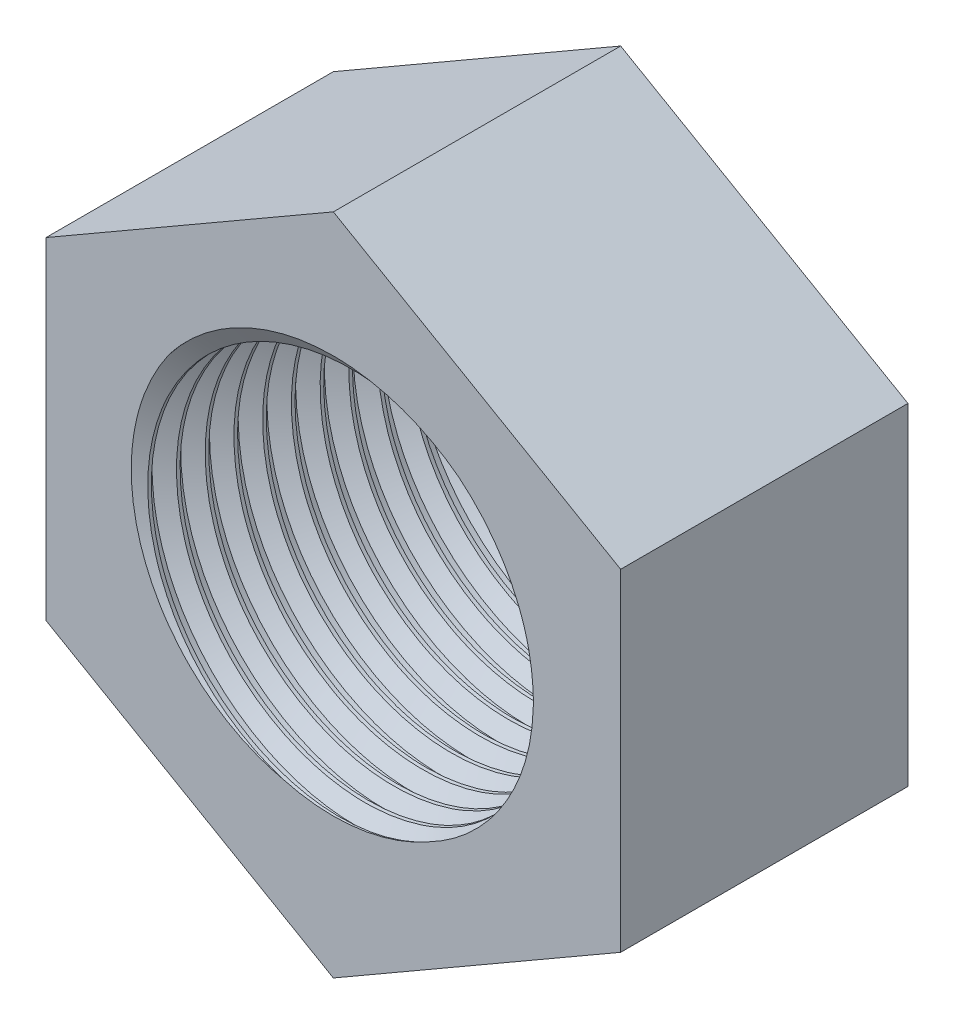
SolidWorks part; units mm, degrees
material "Ductile Iron"
ref_plane "Front Plane" through (0, 0, 0) normal (0, 0, 1) x (1, 0, 0)
ref_plane "Top Plane" through (0, 0, 0) normal (0, 1, 0) x (1, 0, 0)
ref_plane "Right Plane" through (0, 0, 0) normal (1, 0, 0) x (0, 0, -1)
sketch "Sketch1" plane through (0, 0, 0) normal (0, 0, 1) x (1, 0, 0)
  line L1 (0, -17.3205) -> (15, -8.6603)
  line L2 (15, -8.6603) -> (15, 8.6603)
  line L3 (15, 8.6603) -> (0, 17.3205)
  line L4 (0, 17.3205) -> (-15, 8.6603)
  line L5 (-15, 8.6603) -> (-15, -8.6603)
  line L6 (-15, -8.6603) -> (0, -17.3205)
  circle A0 centre (0, 0) radius 15 construction
  circle A1 centre (0, 0) radius 10
  dimension "D2" = 20
  dimension "D1" = 30
extrude "Boss-Extrude1" add sketch "Sketch1" along normal blind 15
thread "Thread1" pitch 1.5 method cut profile "Thread Profile1" start angle 0, offset 10, length 30, pitch 1.5, diameter 20
ref_plane "Plane1" through (-10, 0, 25) normal (0, 1, 0) x (1, 0, 0)
sketch "Thread Profile1" plane through (-10, 0, 25) normal (0, 1, 0) x (1, 0, 0)
  line L0 (0, 0) -> (0, 1.5) construction
  line L11 (0, 0) -> (0, 1.3125)
  line L12 (0, 1.3125) -> (-0.8119, 0.8437)
  line L13 (-0.8119, 0.8437) -> (-0.8119, 0.4687)
  line L15 (-0.8119, 0.4687) -> (0, 0)
  line L17 (-0.8119, 0.6562) -> (0, 0.6562) construction
  point P2 (0, 0)
  dimension "Pitch" = 1.5
  dimension "Profile_Angle" = 60
  dimension "Profile_Land" = 0.375
  dimension "Profile_Height" = 0.8119
